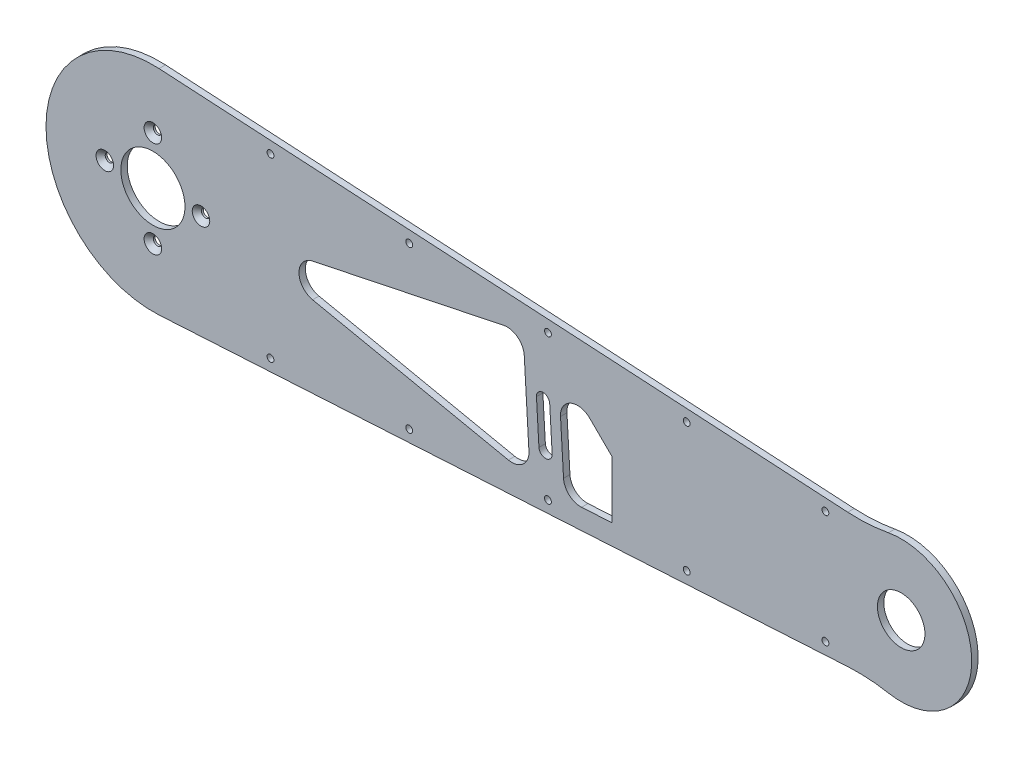
SolidWorks part; units mm, degrees
material "Thornel VCB-20 Carbon Cloth"
ref_plane "Front Plane" through (0, 0, 0) normal (0, 0, 1) x (1, 0, 0)
ref_plane "Top Plane" through (0, 0, 0) normal (0, 1, 0) x (1, 0, 0)
ref_plane "Right Plane" through (0, 0, 0) normal (1, 0, 0) x (0, 0, -1)
sketch "Sketch1" plane through (0, 0, 0) normal (0, 0, 1) x (1, 0, 0)
  line L0 (-175, 0) -> (175, 0) construction
  line L1 (-172.1122, 49.9165) -> (176.7203, 29.7354)
  line L2 (-172.1122, -49.9165) -> (176.7203, -29.7354)
  line L3 (139.566, 26.3757) -> (-120, 41.3925) construction
  line L4 (-55.1085, -37.6383) -> (9.783, -33.8841) construction
  line L5 (-125, 0) -> (-125, 62.9978) construction
  circle A0 centre (175, 0) radius 11.1125
  arc A1 (176.7203, 29.7354) -> (176.7203, -29.7354) centre (175, 0) cw
  circle A3 centre (-175, 0) radius 22.5 construction
  circle A7 centre (-175, 0) radius 15
  circle A9 centre (-120, 41.3925) radius 1.6
  circle A10 centre (-55.1085, 37.6383) radius 1.6
  circle A11 centre (9.783, 33.8841) radius 1.6
  circle A12 centre (74.6745, 30.1299) radius 1.6
  circle A13 centre (139.566, 26.3757) radius 1.6
  circle A15 centre (139.566, -26.3757) radius 1.6
  circle A16 centre (74.6745, -30.1299) radius 1.6
  circle A17 centre (9.783, -33.8841) radius 1.6
  circle A18 centre (-55.1085, -37.6383) radius 1.6
  circle A19 centre (-120, -41.3925) radius 1.6
  arc A20 (-172.1122, 49.9165) -> (-172.1122, -49.9165) centre (-175, 0) ccw
  point P4 (0, 0)
  point P18 (-175, 22.5)
  point P21 (-197.5, 0)
  point P22 (-175, -22.5)
  point P23 (-152.5, 0)
  dimension "D2" = 22.225
  dimension "D3" = 50
  dimension "D5" = 45
  dimension "D6" = 3.2
  dimension "D7" = 260
  dimension "D8" = 5
  dimension "D10" = 30
  dimension "D16" = 5
  dimension "D1" = 350
  dimension "D12" = 5.5
extrude "Boss-Extrude1" add sketch "Sketch1" along normal blind 3
sketch "Sketch4" plane through (0, 0, 3) normal (0, 0, 1) x (1, 0, 0)
  point P10 (-197.5, 0)
  point P13 (-175, 22.5)
  point P16 (-152.5, 0)
  point P19 (-175, -22.5)
hole_wizard "CSK for M3.5 Flat Head Machine Screw1" positions "Sketch4" profile "Sketch6" countersink size "M3.5" standard "ANSI Metric" end condition up to next
sketch "Sketch6" plane through (-197.5, 0, 3) normal (1, 0, 0) x (0, -1, 0)
  line L0 (0, 0) -> (0, 3)
  line L1 (0, 3) -> (1.95, 3)
  line L2 (1.95, 3) -> (1.95, 2.15)
  line L3 (1.95, 2.15) -> (4.1, 0)
  line L5 (4.1, 0) -> (0, 0)
  line L6 (-1.95, 2.15) -> (-4.1, 0) construction
  line L11 (0, -6.35) -> (0, 107.95) construction
  dimension "Thru Hole Dia." = 3.9
  dimension "Thru Hole Depth" = 3
  dimension "Near C'Sink Dia." = 8.2
  dimension "Near C'Sink Angle" = 90
sketch "Sketch7" plane through (0, 0, 3) normal (0, 0, 1) x (1, 0, 0)
  line L0 (74.6745, 30.1299) -> (74.6745, -30.1299) construction
  line L1 (74.6745, -30.1299) -> (139.566, 0) construction
  line L2 (139.566, 0) -> (74.6745, 30.1299) construction
  line L3 (139.566, 0) -> (-152.5, 0) construction
  line L4 (139.566, -26.3757) -> (139.566, 26.3757) construction
  line L5 (51.0999, 37.7683) -> (116.8149, 7.256)
  line L6 (116.8149, -7.256) -> (51.0999, -37.7683)
  line L7 (39.7309, -30.5123) -> (39.7309, 30.5123)
  line L8 (9.783, -33.8841) -> (5.5294, 39.6394) construction
  line L9 (9.783, 33.8841) -> (74.6745, -30.1299) construction
  line L10 (9.783, 33.8841) -> (74.6745, 30.1299) construction
  line L11 (9.783, -33.8841) -> (74.6745, -30.1299) construction
  line L12 (-152.5, 0) -> (-55.1085, 37.6383) construction
  line L13 (-55.1085, 37.6383) -> (9.783, 33.8841) construction
  line L14 (9.783, 33.8841) -> (-152.5, 0) construction
  line L15 (109.6181, -39.853) -> (109.6181, 16.5511)
  line L16 (102.0802, 24.5377) -> (41.3408, 28.0517)
  line L17 (35.2605, 14.3698) -> (95.9999, -45.5482)
  line L18 (29.2743, 9.0376) -> (52.6422, -14.0143)
  line L19 (47.486, -27.6962) -> (25.5253, -28.9667)
  line L20 (17.0766, -21.4421) -> (15.6694, 2.8804)
  line L21 (176.7203, 29.7354) -> (-172.1122, 49.9165) construction
  line L22 (-172.1122, -49.9165) -> (176.7203, -29.7354) construction
  line L23 (0.8889, -18.6602) -> (-1.2973, 19.1278)
  line L24 (-10.9191, 26.4969) -> (-100.3161, 7.8311)
  line L25 (-100.3161, -7.8311) -> (-8.7329, -26.9534)
  line L35 (-197.5, 0) -> (-55.1085, 37.6383) construction
  line L52 (-55.1085, -37.6383) -> (-175, -22.5) construction
  line L53 (-15.2425, -47.7117) -> (-52.5586, -43) construction
  line L54 (-0.7058, -39.4678) -> (2.1851, -39.8329) construction
  line L55 (8.6627, -14.5198) -> (7.5076, 5.4468) construction
  line L56 (5.5679, -14.6989) -> (4.4127, 5.2678)
  line L57 (11.7575, -14.3408) -> (10.6024, 5.6258)
  arc A0 (116.8149, 7.256) -> (116.8149, -7.256) centre (113.4458, 0) cw
  arc A1 (51.0999, -37.7683) -> (39.7309, -30.5123) centre (47.7309, -30.5123) cw
  arc A2 (51.0999, 37.7683) -> (39.7309, 30.5123) centre (47.7309, 30.5123) ccw
  arc A3 (109.6181, 16.5511) -> (102.0802, 24.5377) centre (101.6181, 16.5511) ccw
  arc A4 (41.3408, 28.0517) -> (35.2605, 14.3698) centre (40.8787, 20.065) ccw
  arc A5 (109.6181, -39.853) -> (95.9999, -45.5482) centre (101.6181, -39.853) cw
  arc A6 (52.6422, -14.0143) -> (47.486, -27.6962) centre (47.024, -19.7095) cw
  arc A7 (25.5253, -28.9667) -> (17.0766, -21.4421) centre (25.0632, -20.98) cw
  arc A8 (29.2743, 9.0376) -> (15.6694, 2.8804) centre (23.6561, 3.3424) ccw
  arc A9 (0.8889, -18.6602) -> (-8.7329, -26.9534) centre (-7.0978, -19.1222) cw
  arc A10 (-1.2973, 19.1278) -> (-10.9191, 26.4969) centre (-9.2839, 18.6658) ccw
  arc A11 (-100.3161, 7.8311) -> (-100.3161, -7.8311) centre (-98.681, 0) ccw
  circle A30 centre (-175, 0) radius 15 construction
  circle A31 centre (-175, 0) radius 15 construction
  circle A32 centre (-175, 0) radius 22.5 construction
  circle A49 centre (9.783, -33.8841) radius 1.6 construction
  circle A50 centre (9.783, -33.8841) radius 1.6
  arc A56 (5.5679, -14.6989) -> (11.7575, -14.3408) centre (8.6627, -14.5198) ccw
  arc A57 (10.6024, 5.6258) -> (4.4127, 5.2678) centre (7.5076, 5.4468) ccw
  point P36 (132.4423, 0)
  point P59 (-137.8221, 0)
  point P102 (-15.2425, -47.7117)
  point P126 (8.0851, -4.5365)
  dimension "D8" = 8
  dimension "D12" = 5
  dimension "D20" = 3.1
  dimension "D1" = 3
  dimension "D3" = 8
  dimension "D4" = 8
  dimension "D5" = 8
  dimension "D6" = 16
  dimension "D7" = 6
  dimension "D14" = 5
  dimension "D16" = 24.8967
  dimension "D22" = 20
extrude "Cut-Extrude1" cut sketch "Sketch7" against normal blind 10 contours L57 A57 L56 A56 | L24 A11 L25 A9 L23 A10 | L18 A8 L20 A7 L19 A6 region at (27.5899, -9.9591, 3) region at (-42.4165, -0.2065, 3) region at (8.0851, -4.5365, 3)
sketch "Sketch9" plane through (0, 0, 3) normal (0, 0, 1) x (1, 0, 0)
  line L2 (176.7203, 29.7354) -> (-172.1122, 49.9165) construction
  line L3 (-172.1122, -49.9165) -> (176.7203, -29.7354) construction
  line L4 (254.5375, 0) -> (208, 0) construction
  line L5 (200.557, 2) -> (203.931, 2)
  line L6 (200.557, -2) -> (203.931, -2)
  line L7 (162.9445, 26.3755) -> (155.7345, 26.7926)
  line L8 (162.9445, -26.3755) -> (155.7345, -26.7926)
  arc A1 (155.7345, -26.7926) -> (155.7345, 26.7926) centre (175, 0) ccw
  arc A2 (176.7203, -29.7354) -> (176.7203, 29.7354) centre (175, 0) ccw construction
  arc A3 (200.557, -2) -> (200.557, 2) centre (175, 0) ccw
  arc A4 (162.9445, 26.3755) -> (203.931, 2) centre (175, 0) cw
  arc A5 (203.931, -2) -> (162.9445, -26.3755) centre (175, 0) cw
  dimension "D1" = 33
  dimension "D2" = 4
  dimension "D3" = 4
extrude "Boss-Extrude2" add sketch "Sketch9" against normal up to surface (3 mm away) up to face at (-37.2203, -0.0266, 0)
fillet "Fillet1" radius 1 rebuild error yes
fillet "Fillet2" radius 80 2 edges at (162.5368, 30.556, 1.5) (162.5368, -30.556, 1.5)
